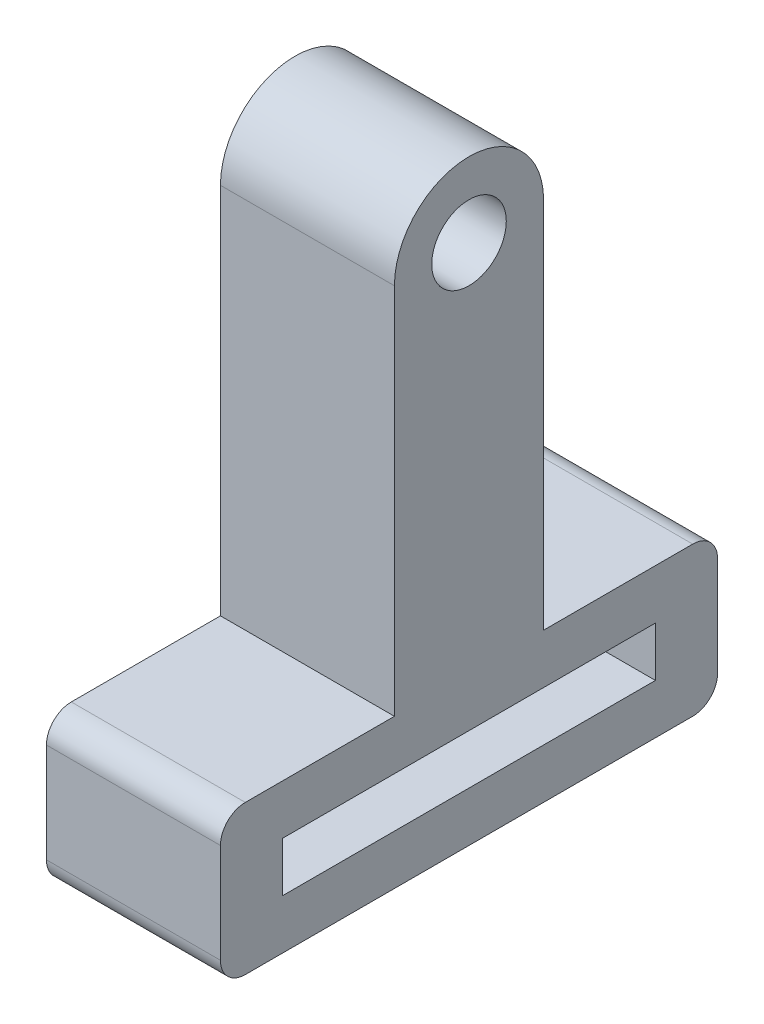
SolidWorks part; units mm, degrees
ref_plane "Alzado" through (0, 0, 0) normal (0, 0, 1) x (1, 0, 0)
ref_plane "Planta" through (0, 0, 0) normal (0, 1, 0) x (1, 0, 0)
ref_plane "Vista lateral" through (0, 0, 0) normal (1, 0, 0) x (0, 0, -1)
sketch "Croquis1" plane through (0, 0, 0) normal (1, 0, 0) x (0, 0, -1)
  line L2 (-10, 3) -> (-10, -3)
  line L3 (-10, -3) -> (10, -3)
  line L4 (10, 3) -> (10, -3)
  line L5 (-10, 3) -> (10, -3) construction
  line L6 (-10, -3) -> (10, 3) construction
  line L7 (-7.5, 1) -> (7.5, 1)
  line L8 (-7.5, 1) -> (-7.5, -1)
  line L9 (-7.5, -1) -> (7.5, -1)
  line L10 (7.5, 1) -> (7.5, -1)
  line L11 (-7.5, 1) -> (7.5, -1) construction
  line L12 (-7.5, -1) -> (7.5, 1) construction
  line L15 (-10, 3) -> (10, 3) construction
  line L27 (-3, 3) -> (-10, 3)
  line L28 (3, 3) -> (10, 3)
  line L35 (0, 3) -> (0, 18) construction
  line L36 (-3, 18) -> (-3, 3)
  line L39 (3, 18) -> (3, 3)
  circle A1 centre (0, 18) radius 1.5
  arc A2 (3, 18) -> (-3, 18) centre (0, 18) ccw
  point P0 (0, 0)
  point P6 (0, 0)
  dimension "D18" = 6
  dimension "D17" = 3
  dimension "D2" = 20
  dimension "D3" = 2
  dimension "D4" = 15
  dimension "D5" = 6
  dimension "D16" = 15
  dimension "D23" = 2
extrude "Saliente-Extruir1" add sketch "Croquis1" along normal mid plane 7
fillet "Redondeo1" radius 1 4 edges at (0, -3, -10) (0, -3, 10) (0, 3, -10) (0, 3, 10)
